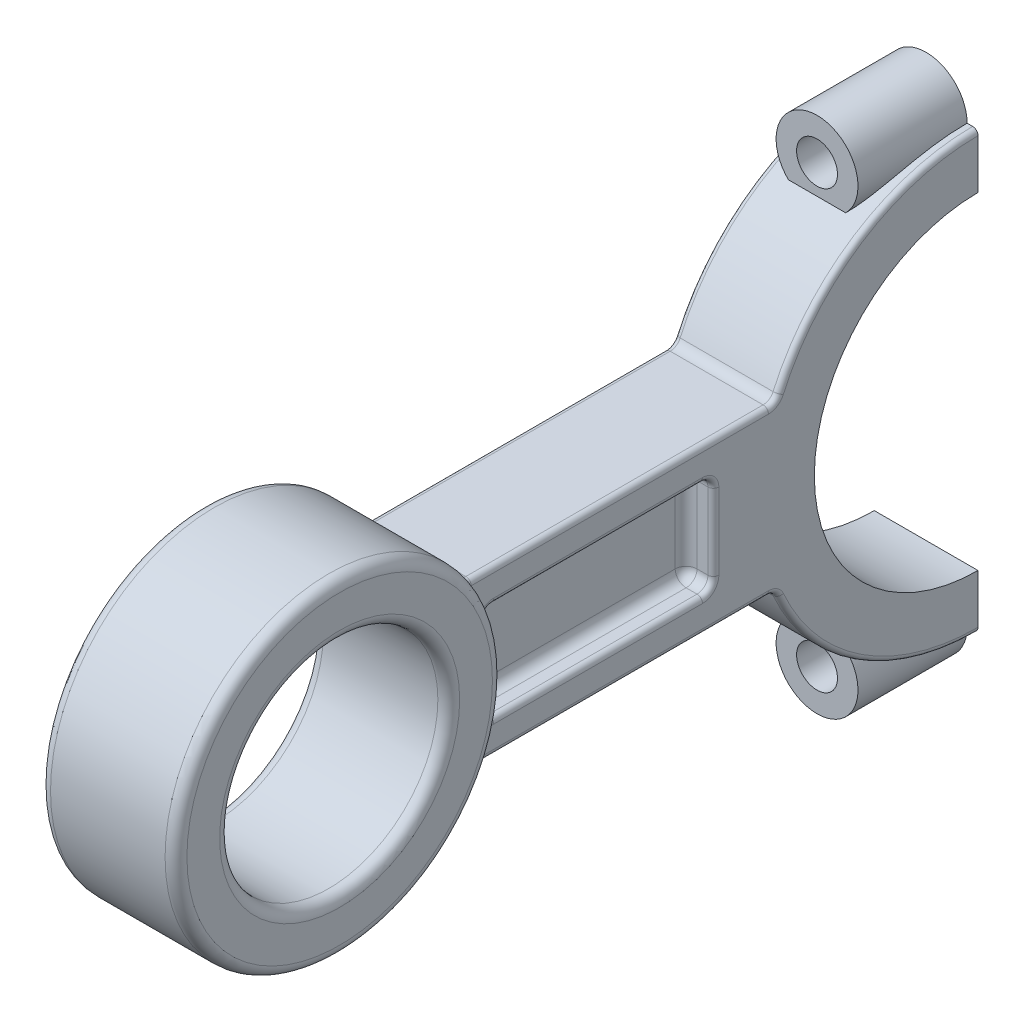
SolidWorks part; units mm, degrees
ref_plane "Front Plane" through (0, 0, 0) normal (0, 0, 1) x (1, 0, 0)
ref_plane "Top Plane" through (0, 0, 0) normal (0, 1, 0) x (1, 0, 0)
ref_plane "Right Plane" through (0, 0, 0) normal (1, 0, 0) x (0, 0, -1)
sketch "Sketch1" plane through (0, 0, 0) normal (1, 0, 0) x (0, 0, -1)
  line L0 (-76.2, 0) -> (76.2, 0) construction
  line L1 (-59.3995, -19.05) -> (29.1071, -19.05)
  line L2 (-59.3995, -19.05) -> (-59.3995, 19.05) construction
  line L3 (-59.3995, 19.05) -> (29.1071, 19.05)
  line L5 (-59.3995, -19.05) -> (59.3995, 19.05) construction
  line L6 (-59.3995, 19.05) -> (59.3995, -19.05) construction
  line L7 (76.2, -50.8) -> (76.2, -38.1)
  line L8 (76.2, 38.1) -> (76.2, 50.8)
  circle A0 centre (-76.2, 0) radius 25.4
  circle A1 centre (-76.2, 0) radius 38.1
  arc A2 (76.2, 38.1) -> (76.2, -38.1) centre (76.2, 0) ccw
  arc A3 (76.2, 50.8) -> (76.2, -50.8) centre (76.2, 0) ccw
  circle A4 centre (76.2, 0) radius 50.8 construction
  circle A5 centre (76.2, 0) radius 38.1 construction
  point P0 (0, 0)
  dimension "D3" = 50.8
  dimension "D5" = 76.2
  dimension "D1" = 152.4
  dimension "D2" = 38.1
  dimension "D4" = 12.7
  dimension "D6" = 12.7
extrude "Boss-Extrude1" add sketch "Sketch1" along normal mid plane 24.13 contours L3 A1 L1 A0 | L1 A1 L3 A0 | A3 L3 A1 L1 | L8 A3 L7 A2 region at (0, 0, 46.7377) region at (0, -20.0922, 51.302) region at (0, 0, 6.576) region at (0, 0, -26.5359)
extrude "Boss-Extrude2" add sketch "Sketch1<3>" along normal mid plane 31.75 contours L3 A1 L1 A0 | L1 A1 L3 A0 region at (0, 0, 46.7377) region at (0, -20.0922, 51.302)
sketch "Sketch1<3>" plane through (0, 0, 0) normal (1, 0, 0) x (0, 0, -1) same geometry as "Sketch1"
sketch "Sketch2" plane through (0, 0, -76.2) normal (0, 0, -1) x (-1, 0, 0)
  line L0 (-12.065, -50.8) -> (12.065, -50.8) construction
  circle A0 centre (0, -50.8) radius 9.525
  dimension "D1" = 19.05
extrude "Boss-Extrude3" add sketch "Sketch2" against normal blind 25.4
sketch "Sketch3" plane through (0, 0, -76.2) normal (0, 0, -1) x (-1, 0, 0)
  circle A0 centre (0, -50.8) radius 4.76
  arc A1 (-9.525, -50.8) -> (9.525, -50.8) centre (0, -50.8) ccw construction
  dimension "D1" = 9.52
extrude "Cut-Extrude1" cut sketch "Sketch3" against normal through all
mirror "Mirror1" about plane through (0, 0, 0) normal (0, 1, 0) of "Cut-Extrude1", "Boss-Extrude3"
sketch "Sketch4" plane through (12.065, 0, 0) normal (1, 0, 0) x (0, 0, -1)
  line L0 (-43.2044, 19.05) -> (29.1071, 19.05) construction
  line L1 (14.6026, -11.43) -> (-39.8549, -11.43)
  line L2 (14.6026, -11.43) -> (14.6026, 11.43)
  line L3 (14.6026, 11.43) -> (-39.8549, 11.43)
  line L4 (-39.8549, -11.43) -> (-39.8549, 11.43) construction
  line L5 (14.6026, -11.43) -> (-39.8549, 11.43) construction
  line L6 (14.6026, 11.43) -> (-39.8549, -11.43) construction
  circle A0 centre (-76.2, 0) radius 38.1 construction
  arc A1 (-39.8549, -11.43) -> (-39.8549, 11.43) centre (-76.2, 0) ccw
  point P0 (-12.6262, 0)
  dimension "D1" = 7.62
extrude "Cut-Extrude2" cut sketch "Sketch4" against normal blind 6.35
mirror "Mirror2" about plane through (0, 0, 0) normal (1, 0, 0) of "Cut-Extrude2"
fillet "Fillet1" radius 2.54 24 edges at (-5.715, -11.43, 12.6262) (-5.715, 0, -14.6026) (-5.715, 11.43, 12.6262) (-5.715, 0, 38.1) (5.715, 11.43, 12.6262) (5.715, 0, -14.6026) (5.715, -11.43, 12.6262) (5.715, 0, 38.1) (-15.875, 0, 50.8) (-15.875, 0, 38.1) (15.875, 0, 50.8) (15.875, 0, 38.1) (8.89, -11.43, -14.6026) (8.89, 11.43, -14.6026) (8.89, 11.43, 39.8549) (8.89, -11.43, 39.8549) (-8.89, -11.43, -14.6026) (-8.89, 11.43, -14.6026) (-8.89, -11.43, 39.8549) (-8.89, 11.43, 39.8549) (0, -19.05, 43.2044) (0, -19.05, -29.1071) (0, 19.05, -29.1071) (0, 19.05, 43.2044)
fillet "Fillet2" radius 1.27 14 edges at (-12.065, -10.4775, 38.527) (-12.065, -11.43, 12.2409) (-12.065, -10.6861, -13.8586) (-12.065, 0, -14.6026) (-12.065, 10.6861, -13.8586) (-12.065, 10.4775, 38.527) (12.065, -10.4775, 38.527) (12.065, -11.43, 12.2409) (12.065, -10.6861, -13.8586) (12.065, 0, -14.6026) (12.065, 10.6861, -13.8586) (12.065, 10.4775, 38.527) (-12.065, 11.43, 12.2409) (12.065, 11.43, 12.2409)
fillet "Fillet3" radius 1.25 16 edges at (-12.065, -19.3675, 42.9989) (-12.065, -42.5746, -48.4863) (-12.065, -19.4613, -28.8104) (-12.065, 19.3675, 42.9989) (-12.065, 42.5746, -48.4863) (-12.065, 19.4613, -28.8104) (12.065, 19.3675, 42.9989) (12.065, 42.5746, -48.4863) (12.065, 19.4613, -28.8104) (12.065, -19.3675, 42.9989) (12.065, -42.5746, -48.4863) (12.065, -19.4613, -28.8104) (-12.065, -19.05, 7.1722) (-12.065, 19.05, 7.1722) (12.065, 19.05, 7.1722) (12.065, -19.05, 7.1722)
